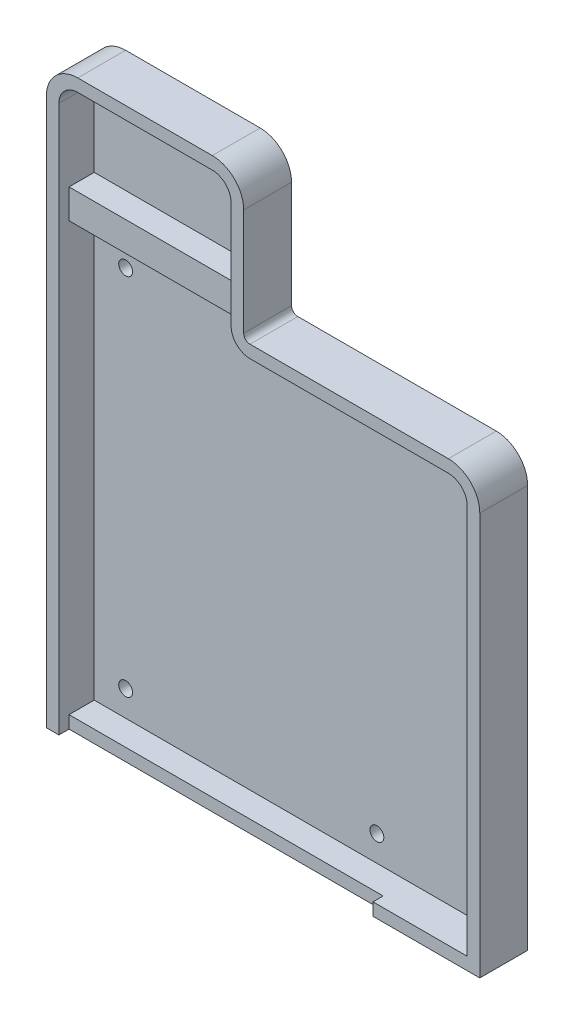
SolidWorks part; units mm, degrees
ref_plane "Front Plane" through (0, 0, 0) normal (0, 0, 1) x (1, 0, 0)
ref_plane "Top Plane" through (0, 0, 0) normal (0, 1, 0) x (1, 0, 0)
ref_plane "Right Plane" through (0, 0, 0) normal (1, 0, 0) x (0, 0, -1)
ref_plane "Plane1" through (200, 247, 0) normal (0, 1, 0) x (1, 0, 0)
sketch "Sketch3" plane through (0, 0, 0) normal (0, 0, 1) x (1, 0, 0)
  line L0 (200, 60) -> (200, 247) construction
  line L1 (200, 161.9071) -> (250, 161.9071)
  line L2 (250, 223.9989) -> (250, 60) construction
  line L3 (227.416, 247) -> (227.416, 230) construction
  line L4 (230.416, 227) -> (247, 227) construction
  line L5 (227.416, 247) -> (227.416, 230)
  line L6 (230.416, 227) -> (247, 227)
  line L7 (203, 250) -> (224.416, 250) construction
  line L9 (200, 161.9071) -> (200, 247)
  line L10 (203, 250) -> (224.416, 250)
  line L12 (198, 159.9071) -> (252, 159.9071)
  line L13 (198, 159.9071) -> (198, 247.0004)
  line L14 (202.9996, 252) -> (224.4164, 252)
  line L15 (229.416, 247.0004) -> (229.416, 230.0004)
  line L16 (230.4164, 229) -> (247.0004, 229)
  line L17 (252, 223.9989) -> (252, 159.9071) construction
  line L18 (250, 223.9989) -> (250, 161.9071) construction
  line L19 (247.0004, 229) -> (261.9985, 229)
  line L20 (247, 227) -> (261.9989, 227)
  line L21 (250, 161.9071) -> (265, 161.9071)
  line L22 (265, 161.9071) -> (265, 223.9989)
  line L23 (266.9996, 223.9989) -> (266.9996, 159.9071)
  line L24 (266.9996, 159.9071) -> (252, 159.9071)
  arc A0 (227.416, 230) -> (230.416, 227) centre (230.4171, 230.0011) ccw construction
  arc A2 (227.416, 230) -> (230.416, 227) centre (230.4171, 230.0011) ccw
  arc A4 (203, 250) -> (200, 247) centre (203.0011, 246.9989) ccw construction
  arc A5 (227.416, 247) -> (224.416, 250) centre (224.4149, 246.9989) ccw construction
  arc A6 (203, 250) -> (200, 247) centre (203.0011, 246.9989) ccw
  arc A7 (227.416, 247) -> (224.416, 250) centre (224.4149, 246.9989) ccw
  arc A8 (202.9996, 252) -> (198, 247.0004) centre (203.0011, 246.9989) ccw
  arc A9 (229.416, 247.0004) -> (224.4164, 252) centre (224.4149, 246.9989) ccw
  arc A10 (229.416, 230.0004) -> (230.4164, 229) centre (230.4171, 230.0011) ccw
  arc A12 (250, 223.9989) -> (247, 227) centre (246.9989, 223.9989) ccw construction
  arc A13 (252, 223.9989) -> (247.0004, 229) centre (246.9989, 223.9989) ccw construction
  arc A14 (265, 223.9989) -> (261.9989, 227) centre (261.9989, 223.9989) ccw
  arc A15 (266.9996, 223.9989) -> (261.9985, 229) centre (261.9985, 223.9989) ccw
  dimension "D1" = 2
sketch "Sketch5" plane through (0, 0, -1.6154) normal (0, 0, -1) x (-1, 0, 0)
  line L0 (-200, 161.9071) -> (-250, 161.9071) construction
  line L1 (-200, 161.9071) -> (-200, 247) construction
  line L2 (-203, 250) -> (-224.416, 250) construction
  line L3 (-227.416, 247) -> (-227.416, 230) construction
  line L4 (-230.416, 227) -> (-247, 227) construction
  line L6 (-200, 161.9071) -> (-250, 161.9071)
  line L7 (-200, 161.9071) -> (-200, 247)
  line L8 (-203, 250) -> (-224.416, 250)
  line L9 (-227.416, 247) -> (-227.416, 230)
  line L10 (-230.416, 227) -> (-247, 227)
  line L12 (-247, 227) -> (-262, 227)
  line L13 (-265, 223.9989) -> (-265, 161.9071)
  line L14 (-265, 161.9071) -> (-250, 161.9071)
  arc A0 (-200, 247) -> (-203, 250) centre (-203.0011, 246.9989) ccw construction
  arc A1 (-224.416, 250) -> (-227.416, 247) centre (-224.4149, 246.9989) ccw construction
  arc A2 (-230.416, 227) -> (-227.416, 230) centre (-230.4171, 230.0011) ccw construction
  arc A4 (-200, 247) -> (-203, 250) centre (-203.0011, 246.9989) ccw
  arc A5 (-224.416, 250) -> (-227.416, 247) centre (-224.4149, 246.9989) ccw
  arc A6 (-230.416, 227) -> (-227.416, 230) centre (-230.4171, 230.0011) ccw
  arc A8 (-262, 227) -> (-265, 223.9989) centre (-262, 224) ccw
extrude "Boss-Extrude1" add sketch "Sketch3" against normal blind 7.62
extrude "Boss-Extrude2" add sketch "Sketch5" along normal up to vertex (6.0046 mm away) separate body up to point (227.416, 230, -7.62)
sketch "Sketch9" plane through (0, 0, -1.6154) normal (0, 0, 1) x (1, 0, 0)
  line L2 (261.9989, 227) -> (230.416, 227) construction
  line L3 (227.416, 230) -> (227.416, 247) construction
  line L4 (224.416, 250) -> (203, 250) construction
  line L5 (200, 247) -> (200, 161.9071) construction
  line L9 (227.416, 230) -> (227.416, 247)
  line L10 (224.416, 250) -> (203, 250)
  line L11 (200, 247) -> (200, 161.9071)
  line L12 (265, 161.9071) -> (200, 161.9071) construction
  line L14 (265, 223.9989) -> (265, 161.9071) construction
  line L15 (265, 161.9071) -> (200, 161.9071)
  line L17 (265, 223.9989) -> (265, 161.9071)
  line L18 (230.416, 227) -> (261.9989, 227)
  arc A1 (227.416, 230) -> (230.416, 227) centre (230.4171, 230.0011) ccw construction
  arc A2 (227.416, 247) -> (224.416, 250) centre (224.4149, 246.9989) ccw construction
  arc A3 (203, 250) -> (200, 247) centre (203.0011, 246.9989) ccw construction
  arc A5 (227.416, 230) -> (230.416, 227) centre (230.4171, 230.0011) ccw
  arc A6 (227.416, 247) -> (224.416, 250) centre (224.4149, 246.9989) ccw
  arc A7 (203, 250) -> (200, 247) centre (203.0011, 246.9989) ccw
  arc A9 (265, 223.9989) -> (261.9989, 227) centre (261.9989, 223.9989) ccw
sketch "Sketch11" plane through (0, 159.9071, 0) normal (0, -1, 0) x (1, 0, 0)
  line L0 (200, 0) -> (200, -1.6154)
  line L1 (200, -1.6154) -> (250, -1.6154)
  line L4 (250, -1.6154) -> (250, 0)
  line L5 (198, 0) -> (266.9996, 0) construction
  line L6 (250, 0) -> (200, 0)
sketch "Sketch12" plane through (0, 0, -1.6154) normal (0, 0, -1) x (-1, 0, 0)
  circle A0 centre (-205, 224) radius 1.1 construction
  circle A1 centre (-225, 224) radius 1.1 construction
  circle A2 centre (-205, 166) radius 1.1 construction
  circle A3 centre (-245, 166) radius 1.1 construction
  circle A4 centre (-205, 224) radius 1.1
  circle A5 centre (-225, 224) radius 1.1
  circle A6 centre (-205, 166) radius 1.1
  circle A7 centre (-245, 166) radius 1.1
  circle A8 centre (-245, 166) radius 2.1
  circle A9 centre (-205, 166) radius 2.1
  circle A10 centre (-225, 224) radius 2.1
  circle A11 centre (-205, 224) radius 2.1
  dimension "D1" = 1
sketch "Sketch13" plane through (0, 0, -1.6154) normal (0, 0, -1) x (-1, 0, 0)
  circle A0 centre (-225, 224) radius 1.1 construction
  circle A1 centre (-205, 224) radius 1.1 construction
  circle A2 centre (-205, 166) radius 1.1 construction
  circle A3 centre (-245, 166) radius 1.1 construction
  circle A4 centre (-225, 224) radius 1.1
  circle A5 centre (-205, 224) radius 1.1
  circle A6 centre (-205, 166) radius 1.1
  circle A7 centre (-245, 166) radius 1.1
extrude "Boss-Extrude5" add sketch "Sketch12" along normal up to surface (6.0046 mm away) up to face at (230.4665, 222.7056, -7.62)
extrude "Cut-Extrude5" cut sketch "Sketch13" along normal up to surface (6.0046 mm away) up to face at (230.9491, 223.2713, -7.62)
extrude "Cut-Extrude6" cut sketch "Sketch11" against normal up to surface (2 mm away) up to face at (232.5, 161.9071, -0.8077)
extrude "Cut-Extrude8" cut sketch "Sketch9" against normal offset from surface (4.0046 mm away) 2 up to face at (246.1, 166, -7.62)
sketch "Sketch14" plane through (0, 0, -5.62) normal (0, 0, 1) x (1, 0, 0)
  line L0 (200, 161.9071) -> (200, 247) construction
  line L1 (227.416, 230) -> (200, 230)
  line L2 (227.416, 230) -> (227.416, 234.6663)
  line L3 (227.416, 234.6663) -> (200, 234.6663)
  line L4 (200, 230) -> (200, 234.6663)
extrude "Boss-Extrude7" add sketch "Sketch14" along normal up to vertex (4.0046 mm away) up to point (200, 161.9071, -1.6154)
